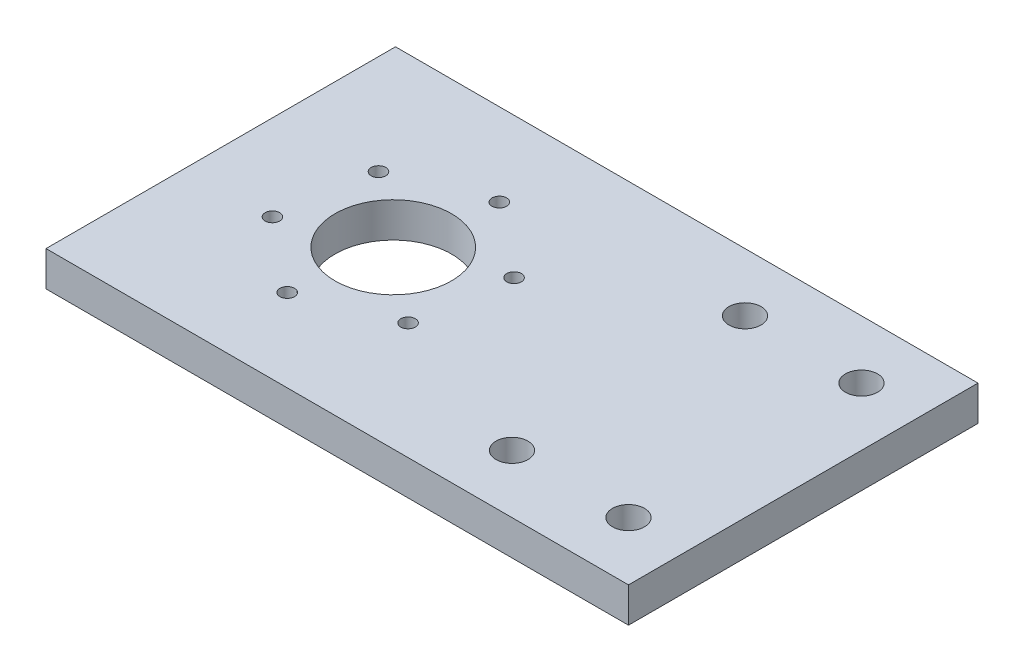
SolidWorks part; units mm, degrees
ref_plane "Front Plane" through (0, 0, 0) normal (0, 0, 1) x (1, 0, 0)
ref_plane "Top Plane" through (0, 0, 0) normal (0, 1, 0) x (1, 0, 0)
ref_plane "Right Plane" through (0, 0, 0) normal (1, 0, 0) x (0, 0, -1)
sketch "Sketch1" plane through (0, 0, 0) normal (0, 1, 0) x (1, 0, 0)
  line L1 (0, 0) -> (100, 0)
  line L2 (0, 0) -> (0, 60)
  line L3 (0, 60) -> (100, 60)
  line L4 (100, 0) -> (100, 60)
  dimension "D1" = 100
  dimension "D2" = 60
extrude "Boss-Extrude1" add sketch "Sketch1" along normal blind 6
sketch "Sketch2" plane through (0, 6, 0) normal (0, 1, 0) x (1, 0, 0)
  line L1 (100, 0) -> (100, 60) construction
  line L7 (100, 30) -> (0, 30) construction
  line L8 (0, 60) -> (0, 0) construction
  circle A0 centre (29.6153, 30) radius 10
  circle A5 centre (70, 50) radius 2.75
  circle A6 centre (90, 50) radius 2.75
  circle A7 centre (70, 10) radius 2.75
  circle A8 centre (90, 10) radius 2.75
  point P7 (100, 30)
  dimension "D1" = 20
extrude "Cut-Extrude1" cut sketch "Sketch2" against normal blind 6
sketch "Sketch3" plane through (0, 6, 0) normal (0, 1, 0) x (1, 0, 0)
  circle A0 centre (31.9984, 45.8215) radius 1.25 construction
  circle A1 centre (31.9984, 45.8215) radius 1.25
  circle A2 centre (17.105, 39.9745) radius 1.25 construction
  circle A3 centre (17.105, 39.9745) radius 1.25
  circle A4 centre (44.5087, 35.847) radius 1.25 construction
  circle A5 centre (14.722, 24.153) radius 1.25 construction
  circle A6 centre (27.2323, 14.1785) radius 1.25 construction
  circle A7 centre (42.1257, 20.0255) radius 1.25 construction
  circle A8 centre (31.9984, 45.8215) radius 1.25
  circle A9 centre (44.5087, 35.847) radius 1.25
  circle A10 centre (17.105, 39.9745) radius 1.25
  circle A11 centre (14.722, 24.153) radius 1.25
  circle A12 centre (27.2323, 14.1785) radius 1.25
  circle A13 centre (42.1257, 20.0255) radius 1.25
extrude "Cut-Extrude2" cut sketch "Sketch3" against normal through all contours A1 | A9 | A13 | A12 | A11 | A3 region at (31.9984, 6, -45.8215) region at (44.5087, 6, -35.847) region at (14.722, 6, -24.153) region at (27.2323, 6, -14.1785) region at (42.1257, 6, -20.0255)
